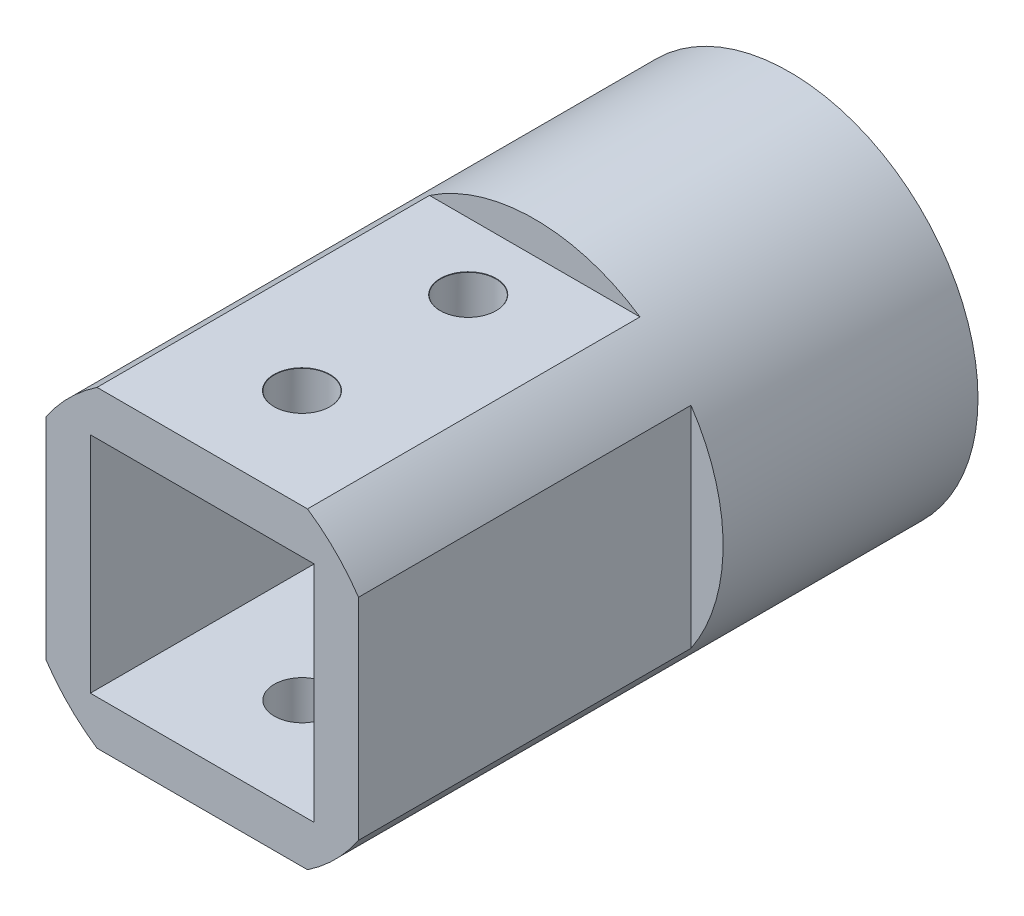
SolidWorks part; units mm, degrees
ref_plane "前视基准面" through (0, 0, 0) normal (0, 0, 1) x (1, 0, 0)
ref_plane "上视基准面" through (0, 0, 0) normal (0, 1, 0) x (1, 0, 0)
ref_plane "右视基准面" through (0, 0, 0) normal (1, 0, 0) x (0, 0, -1)
sketch "草图1" plane through (0, 0, 0) normal (0, 0, 1) x (1, 0, 0)
  circle A0 centre (0, 0) radius 17
  dimension "D1" = 34
extrude "凸台-拉伸1" add sketch "草图1" along normal blind 3
sketch "草图2" plane through (0, 0, 3) normal (0, 0, 1) x (1, 0, 0)
  circle A0 centre (0, 0) radius 17 construction
  circle A1 centre (0, 0) radius 17
  circle A2 centre (0, 0) radius 15
  dimension "D1" = 30
extrude "凸台-拉伸2" add sketch "草图2" along normal blind 10
sketch "草图3" plane through (0, 0, 3) normal (0, 0, 1) x (1, 0, 0)
  circle A0 centre (0, 0) radius 5
  dimension "D1" = 10
extrude "切除-拉伸1" cut sketch "草图3" against normal through all
sketch "草图4" plane through (0, 0, 13) normal (0, 0, 1) x (1, 0, 0)
  line L0 (0, 17) -> (0, -17) construction
  line L1 (-17, 0) -> (0, 0) construction
  line L2 (-4.4431, 10.1) -> (4.4431, 10.1)
  line L7 (10.1, 4.4431) -> (10.1, -4.4431)
  line L8 (-10.1, 4.4431) -> (-10.1, -4.4431)
  line L9 (-4.4431, 10.1) -> (-10.1, 4.4431)
  line L10 (4.4431, 10.1) -> (10.1, 4.4431)
  line L11 (-4.4431, -10.1) -> (-10.1, -4.4431)
  line L12 (-4.4431, -10.1) -> (4.4431, -10.1)
  line L13 (4.4431, -10.1) -> (10.1, -4.4431)
  circle A0 centre (0, 0) radius 17
  point P17 (0, 10.1)
  point P18 (-10.1, 0)
  point P21 (10.1, 0)
  dimension "D1" = 10.1
  dimension "D2" = 10.1
  dimension "D3" = 8
  dimension "D4" = 135
extrude "凸台-拉伸3" add sketch "草图4" along normal blind 10
sketch "草图5" plane through (0, 0, 23) normal (0, 0, 1) x (1, 0, 0)
  line L2 (-9.4968, 14.1) -> (9.4968, 14.1)
  line L4 (-14.1, 9.4968) -> (-14.1, -9.4968)
  line L6 (0, 0) -> (10.1, 10.1) construction
  line L7 (14.1, -9.4968) -> (14.1, 9.4968)
  line L8 (9.4968, -14.1) -> (-9.4968, -14.1)
  line L11 (-10.1, 10.1) -> (-10.1, -10.1)
  line L12 (-10.1, -10.1) -> (10.1, -10.1)
  line L13 (10.1, -10.1) -> (10.1, 10.1)
  line L14 (10.1, 10.1) -> (-10.1, 10.1)
  circle A1 centre (0, 0) radius 17 construction
  arc A2 (-14.1, -9.4968) -> (-9.4968, -14.1) centre (0, 0) ccw
  arc A3 (-9.4968, 14.1) -> (-14.1, 9.4968) centre (0, 0) ccw
  arc A4 (14.1404, 9.4366) -> (9.4366, 14.1404) centre (0, 0) ccw
  arc A5 (14.1, -9.4968) -> (9.4968, -14.1) centre (0, 0) cw
  circle M7 centre (0, 0) radius 17
  dimension "D1" = 4
  dimension "D2" = 4
  dimension "D3" = 20.2
  dimension "D4" = 20.2
extrude "凸台-拉伸4" add sketch "草图5" along normal blind 30 contours L6 A4 L2 L4 M7 | L6 A2 L8 L7 M7 region at (0, 13.7012, 23)
hole_wizard "Ø5.0mm 暗销孔1" positions "草图6" profile "草图7" hole size "Ø5.0" standard "ISO" end condition through all
sketch "草图6" plane through (0, 14.1, 0) normal (0, 1, 0) x (1, 0, 0)
  line L2 (-9.4968, -23) -> (9.4968, -23) construction
  point P0 (0, -29)
  point P2 (0, -44)
  dimension "D1" = 6
  dimension "D2" = 15
sketch "草图7" plane through (0, 14.1, 29) normal (1, 0, 0) x (0, 0, 1)
  line L0 (0, 0) -> (0, 31.1)
  line L1 (0, 31.1) -> (2.5, 31.1)
  line L2 (2.5, 31.1) -> (2.5, 0.025)
  line L3 (2.5, 0.025) -> (2.525, 0)
  line L5 (2.525, 0) -> (0, 0)
  line L6 (-2.5, 0.025) -> (-2.525, 0) construction
  line L11 (0, -6.35) -> (0, 107.95) construction
  dimension "通孔孔直径" = 5
  dimension "通孔孔深度" = 31.1
  dimension "近端锥形沉头孔直径" = 5.05
  dimension "近端锥形沉头孔角度" = 90
hole_wizard "Ø2.5mm 暗销孔1" positions "草图9" profile "草图10" hole size "Ø2.5" standard "ISO" end condition through all
sketch "草图9" plane through (0, 0, 3) normal (0, 0, 1) x (1, 0, 0)
  point P0 (0, 8)
  point P11 (8, 0)
  point P12 (0, -8)
  point P13 (-8, 0)
  dimension "D1" = 8
  dimension "D2" = 4
sketch "草图10" plane through (0, 8, 3) normal (1, 0, 0) x (0, -1, 0)
  line L0 (0, 0) -> (0, 3)
  line L1 (0, 3) -> (1.25, 3)
  line L2 (1.25, 3) -> (1.25, 0.025)
  line L3 (1.25, 0.025) -> (1.275, 0)
  line L5 (1.275, 0) -> (0, 0)
  line L6 (-1.25, 0.025) -> (-1.275, 0) construction
  line L11 (0, -6.35) -> (0, 107.95) construction
  dimension "通孔孔直径" = 2.5
  dimension "通孔孔深度" = 3
  dimension "近端锥形沉头孔直径" = 2.55
  dimension "近端锥形沉头孔角度" = 90
